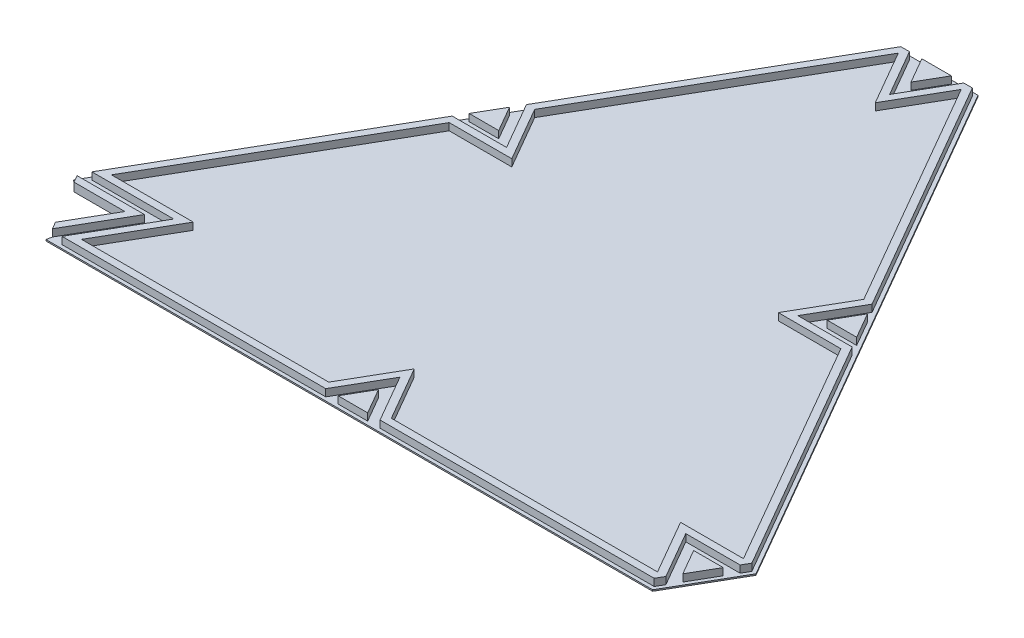
SolidWorks part; units mm, degrees
ref_plane "Front Plane" through (0, 0, 0) normal (0, 0, 1) x (1, 0, 0)
ref_plane "Top Plane" through (0, 0, 0) normal (0, 1, 0) x (1, 0, 0)
ref_plane "Right Plane" through (0, 0, 0) normal (1, 0, 0) x (0, 0, -1)
sketch "Sketch1" plane through (0, 0, 0) normal (0, 1, 0) x (1, 0, 0)
  line L17 (-84.5662, 18.8923) -> (-84.5662, 18.3923) construction
  line L24 (-89.7106, 9.9821) -> (-89.2776, 10.2321) construction
  line L25 (-79.4219, 9.9821) -> (-79.8549, 10.2321) construction
  line L27 (-84.5662, 2.0718) -> (-75.1436, 18.3923)
  line L28 (-93.9889, 18.3923) -> (-75.1436, 18.3923)
  line L29 (-2.5, 5.4019) -> (-2.067, 5.1519) construction
  line L58 (2.5, 5.4019) -> (2.067, 5.1519) construction
  line L59 (0, 1.0718) -> (0, 1.5718) construction
  line L65 (-4.134, 1.5718) -> (4.134, 1.5718)
  line L69 (0, 8.7321) -> (4.134, 1.5718)
  line L71 (-4.134, 1.5718) -> (0, 8.7321)
  line L79 (87.2106, 14.3122) -> (87.2106, 13.8122) construction
  line L81 (84.7106, 9.9821) -> (85.1436, 10.2321) construction
  line L135 (89.7106, 9.9821) -> (89.2776, 10.2321) construction
  line L138 (83.0766, 13.8122) -> (91.3446, 13.8122)
  line L146 (87.2106, 6.6519) -> (91.3446, 13.8122)
  line L149 (83.0766, 13.8122) -> (87.2106, 6.6519)
  line L157 (47.5718, 92.1288) -> (48.0048, 91.8788) construction
  line L158 (52.5718, 92.1288) -> (52.1388, 91.8788) construction
  line L160 (50.0718, 87.7987) -> (50.0718, 88.2987) construction
  line L161 (45.9378, 88.2987) -> (54.2058, 88.2987)
  line L162 (50.0718, 95.4589) -> (54.2058, 88.2987)
  line L163 (45.9378, 88.2987) -> (50.0718, 95.4589)
  line L164 (0, 165.3653) -> (0, 164.8653) construction
  line L165 (-2.5, 161.0352) -> (-2.067, 161.2852) construction
  line L166 (2.5, 161.0352) -> (2.067, 161.2852) construction
  line L167 (-4.134, 164.8653) -> (4.134, 164.8653)
  line L168 (0, 157.7051) -> (4.134, 164.8653)
  line L169 (-4.134, 164.8653) -> (0, 157.7051)
  line L170 (-52.5718, 92.1288) -> (-52.1388, 91.8788) construction
  line L171 (-47.5718, 92.1288) -> (-48.0048, 91.8788) construction
  line L172 (-50.0718, 87.7987) -> (-50.0718, 88.2987) construction
  line L173 (-54.2058, 88.2987) -> (-45.9378, 88.2987)
  line L174 (-50.0718, 95.4589) -> (-45.9378, 88.2987)
  line L175 (-54.2058, 88.2987) -> (-50.0718, 95.4589)
  line L176 (-76.5352, 10.9821) -> (-76.1021, 10.7321) construction
  line L177 (-69.9474, 21.3923) -> (-81.3908, 1.5718)
  line L178 (-3.6547, 7.4019) -> (-4.0877, 7.6519) construction
  line L179 (0, 14.7321) -> (-7.5981, 1.5718)
  line L180 (-7.5981, 1.5718) -> (-81.3908, 1.5718)
  line L181 (3.6547, 7.4019) -> (4.0877, 7.6519) construction
  line L182 (82.4012, 9.9821) -> (81.9682, 9.7321) construction
  line L183 (0, 14.7321) -> (7.5981, 1.5718)
  line L184 (85.3111, 2.3619) -> (84.878, 2.6119) construction
  line L185 (7.5981, 1.5718) -> (84.2776, 1.5718)
  line L186 (85.4785, 3.6519) -> (84.2776, 1.5718)
  line L187 (77.8805, 16.8122) -> (85.4785, 3.6519)
  line L188 (86.0559, 16.3122) -> (86.0559, 16.8122) construction
  line L189 (94.1101, 17.6022) -> (93.6771, 17.8522) construction
  line L190 (77.8805, 16.8122) -> (93.0766, 16.8122)
  line L191 (94.2776, 18.8923) -> (93.0766, 16.8122)
  line L192 (75.5407, 52.3455) -> (75.1077, 52.0955) construction
  line L193 (55.9378, 85.2987) -> (94.2776, 18.8923)
  line L194 (48.3397, 85.2987) -> (48.3397, 83.2987) construction
  line L195 (40.7417, 85.2987) -> (55.9378, 85.2987)
  line L196 (45.2624, 92.1288) -> (44.8294, 92.3788) construction
  line L197 (29.6029, 131.9121) -> (29.1699, 131.6621) construction
  line L198 (10, 164.8653) -> (48.3397, 98.4589)
  line L199 (40.7417, 85.2987) -> (48.3397, 98.4589)
  line L200 (8.799, 165.3653) -> (8.799, 164.8653) construction
  line L201 (7.5981, 164.8653) -> (10, 164.8653)
  line L202 (3.6547, 159.0352) -> (4.0877, 158.7852) construction
  line L203 (7.5981, 164.8653) -> (0, 151.7051)
  line L204 (-8.799, 165.3653) -> (-8.799, 164.8653) construction
  line L205 (-3.6547, 159.0352) -> (-4.0877, 158.7852) construction
  line L206 (-29.6029, 131.9121) -> (-29.1699, 131.6621) construction
  line L207 (-48.3397, 98.4589) -> (-10, 164.8653)
  line L208 (-10, 164.8653) -> (-7.5981, 164.8653)
  line L209 (0, 151.7051) -> (-7.5981, 164.8653)
  line L210 (-45.2624, 92.1288) -> (-44.8294, 92.3788) construction
  line L211 (-48.3397, 98.4589) -> (-40.7417, 85.2987)
  line L212 (-48.3397, 85.2987) -> (-48.3397, 83.2987) construction
  line L213 (-74.9634, 53.3455) -> (-74.5303, 53.0955) construction
  line L214 (-92.8342, 21.3923) -> (-55.9378, 85.2987)
  line L215 (-55.9378, 85.2987) -> (-40.7417, 85.2987)
  line L216 (-82.2568, 20.8923) -> (-82.2568, 21.3923) construction
  line L217 (-92.8342, 21.3923) -> (-69.9474, 21.3923)
  line L218 (-44.7831, 1.0718) -> (-44.7831, 0.5718) construction
  line L219 (-84.8549, 0.5718) -> (84.8549, 0.5718)
  line L220 (-89.7106, 9.9821) -> (-90.1436, 9.7321) construction
  line L222 (0, 165.3653) -> (0, 165.8653) construction
  line L223 (10.5774, 165.8653) -> (-10.5774, 165.8653)
  line L224 (-95.4323, 18.8923) -> (-10.5774, 165.8653)
  line L225 (52.5718, 92.1288) -> (53.0048, 92.3788) construction
  line L226 (95.4323, 18.8923) -> (10.5774, 165.8653)
  line L227 (89.7106, 9.9821) -> (90.1436, 9.7321) construction
  line L228 (84.8549, 0.5718) -> (95.4323, 18.8923)
  line L229 (-84.5662, 18.3923) -> (-84.5662, 16.3923) construction
  line L230 (-79.8549, 10.2321) -> (-81.587, 11.2321) construction
  line L232 (-89.2776, 10.2321) -> (-87.5455, 11.2321) construction
  line L235 (-95.4323, 18.8923) -> (-93.9889, 18.3923)
  line L236 (-84.8549, 0.5718) -> (-84.5662, 2.0718)
  line L238 (-92.8342, 16.3923) -> (-78.6077, 16.3923)
  line L239 (-78.6077, 16.3923) -> (-85.7209, 4.0718)
  line L240 (-93.9889, 18.3923) -> (-92.8342, 16.3923)
  line L241 (-85.7209, 4.0718) -> (-84.5662, 2.0718)
  line L242 (-44.4944, 1.5718) -> (-44.4944, 3.5718) construction
  line L243 (-75.6691, 11.4821) -> (-73.9371, 10.4821) construction
  line L244 (-77.9267, 3.5718) -> (-66.4833, 23.3923)
  line L245 (-77.9267, 3.5718) -> (-8.7528, 3.5718)
  line L246 (-3.799, 8.1519) -> (-5.5311, 9.1519) construction
  line L247 (-8.7528, 3.5718) -> (0, 18.7321)
  line L248 (4.0877, 7.6519) -> (5.8198, 8.6519) construction
  line L249 (45.9378, 1.5718) -> (45.9378, 3.5718) construction
  line L250 (0, 18.7321) -> (8.7528, 3.5718)
  line L251 (81.9682, 9.7321) -> (80.2361, 8.7321) construction
  line L252 (45.9378, 3.5718) -> (8.7528, 3.5718)
  line L253 (74.4164, 18.8122) -> (83.2154, 3.5718)
  line L254 (45.9378, 3.5718) -> (83.2154, 3.5718)
  line L255 (85.4785, 16.8122) -> (85.4785, 18.8122) construction
  line L256 (74.4164, 18.8122) -> (92.0144, 18.8122)
  line L257 (75.1077, 52.0955) -> (73.3756, 51.0955) construction
  line L258 (44.8294, 92.3788) -> (43.0973, 93.3788) construction
  line L259 (54.7831, 83.2987) -> (92.0144, 18.8122)
  line L260 (54.7831, 83.2987) -> (37.2776, 83.2987)
  line L261 (46.0303, 98.4589) -> (37.2776, 83.2987)
  line L262 (29.1699, 131.6621) -> (27.4378, 130.6621) construction
  line L263 (46.0303, 98.4589) -> (8.799, 162.9455)
  line L264 (4.0877, 158.7852) -> (5.8198, 157.7852) construction
  line L265 (0, 147.7051) -> (8.799, 162.9455)
  line L266 (-3.218, 157.2789) -> (-4.9501, 156.2789) construction
  line L267 (-8.799, 162.9455) -> (0, 147.7051)
  line L268 (-29.1699, 131.6621) -> (-27.4378, 130.6621) construction
  line L269 (-8.799, 162.9455) -> (-46.0303, 98.4589)
  line L270 (-44.5407, 91.8788) -> (-42.8087, 92.8788) construction
  line L271 (-46.0303, 98.4589) -> (-37.2776, 83.2987)
  line L272 (-54.7831, 83.2987) -> (-37.2776, 83.2987)
  line L273 (-72.465, 56.6729) -> (-70.7329, 55.6729) construction
  line L274 (-54.7831, 83.2987) -> (-89.3701, 23.3923)
  line L275 (-81.3908, 21.3923) -> (-81.3908, 23.3923) construction
  line L276 (-89.3701, 23.3923) -> (-66.4833, 23.3923)
  point P9 (-89.2776, 10.2321)
  point P12 (-79.8549, 10.2321)
  point P15 (-84.5662, 18.3923)
  point P21 (0, 1.5718)
  point P24 (2.067, 5.1519)
  point P27 (-2.067, 5.1519)
  point P32 (87.2106, 13.8122)
  point P36 (89.2776, 10.2321)
  point P41 (85.1436, 10.2321)
  point P48 (50.0718, 88.2987)
  point P49 (-84.5662, 16.3923)
  point P51 (50.0718, 88.2987)
  point P54 (52.1388, 91.8788)
  point P58 (48.0048, 91.8788)
  point P64 (-81.587, 11.2321)
  point P68 (-87.5455, 11.2321)
  point P74 (0, 164.8653)
  point P76 (-73.9371, 10.4821)
  point P81 (-44.4944, 3.5718)
  point P84 (-5.5311, 9.1519)
  point P87 (5.8198, 8.6519)
  point P89 (2.067, 161.2852)
  point P95 (80.2361, 8.7321)
  point P97 (-2.067, 161.2852)
  point P105 (85.4785, 18.8122)
  point P106 (-50.0718, 88.2987)
  point P109 (-50.0718, 88.2987)
  point P114 (-48.0048, 91.8788)
  point P118 (48.3397, 83.2987)
  point P119 (-52.1388, 91.8788)
  point P123 (-76.1021, 10.7321)
  point P131 (-4.0877, 7.6519)
  point P138 (4.0877, 7.6519)
  point P144 (84.878, 2.6119)
  point P146 (81.9682, 9.7321)
  point P151 (86.0559, 16.8122)
  point P154 (93.6771, 17.8522)
  point P156 (75.1077, 52.0955)
  point P157 (27.4378, 130.6621)
  point P168 (44.8294, 92.3788)
  point P172 (8.799, 164.8653)
  point P176 (4.0877, 158.7852)
  point P184 (-8.799, 164.8653)
  point P187 (-29.1699, 131.6621)
  point P191 (-44.8294, 92.3788)
  point P198 (-74.5303, 53.0955)
  point P204 (-82.2568, 21.3923)
  point P208 (-90.1436, 9.7321)
  point P212 (0, 165.8653)
  point P214 (0, 165.8653)
  point P217 (53.0048, 92.3788)
  point P218 (5.8198, 157.7852)
  point P220 (90.1436, 9.7321)
  point P226 (-27.4378, 130.6621)
  point P230 (-42.8087, 92.8788)
  point P231 (-42.8087, 92.8788)
  point P237 (-81.3908, 23.3923)
  dimension "D1" = 0.5
  dimension "D2" = 0.5
extrude "Boss-Extrude1" add sketch "Sketch1" along normal blind 2.38 contours L214 L217 L177 L180 L179 L183 L185 L186 L187 L190 L191 L193 L195 L199 L198 L201 L203 L209 L208 L207 L211 L215 | L239 L241 L27 L28 L240 L238 | L173 L174 L175 | L65 L69 L71 | L138 L146 L149 | L161 L162 L163 | L167 L168 L169 region at (-84.9277, 0, -3.1964) region at (-81.3908, 0, -21.6407)
extrude "Boss-Extrude4" add sketch "Sketch1<8>" along normal blind 0.38 contours L219 L228 L226 L223 L224 L173 L175 L174 L161 L163 L162 L65 L71 L69 L28 L27 L149 L138 L146 L169 L167 L168 L217 L214 L215 L211 L207 L208 L209 L203 L201 L198 L199 L195 L193 L191 L190 L187 L186 L185 L183 L179 | L276 L244 L245 L247 L250 L252 L254 L253 L256 L259 L260 L261 L263 L265 L267 L269 L271 L272 L274 region at (-77.6683, 0, -8.9696)
sketch "Sketch1<8>" plane through (0, 0, 0) normal (0, 1, 0) x (1, 0, 0) same geometry as "Sketch1"
